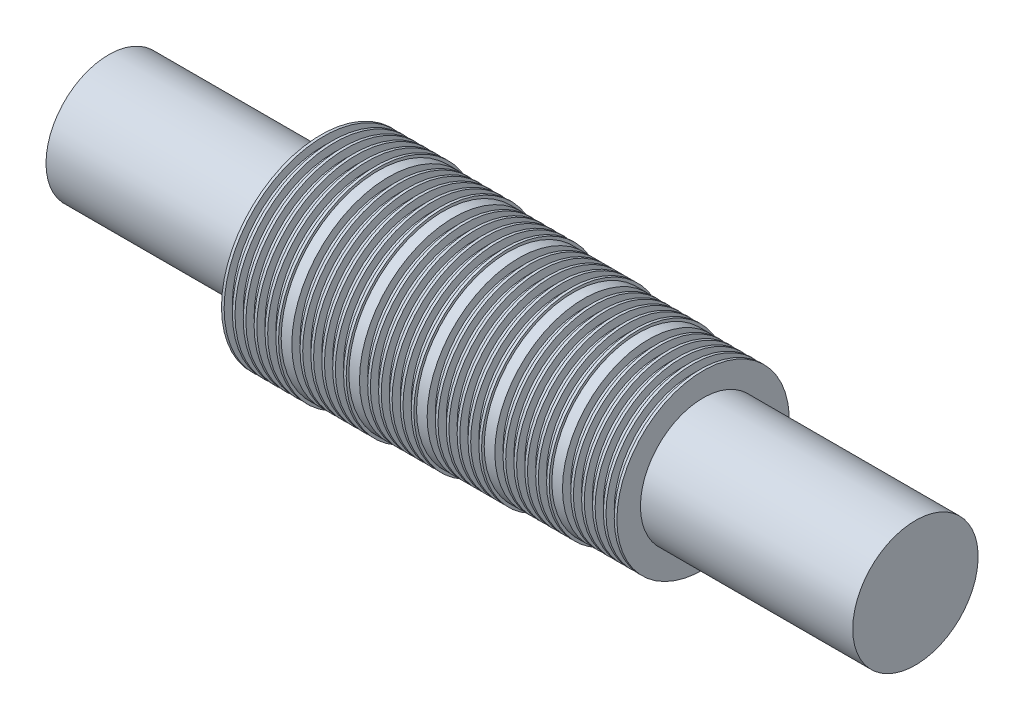
SolidWorks part; units mm, degrees
ref_plane "Front Plane" through (0, 0, 0) normal (0, 0, 1) x (1, 0, 0)
ref_plane "Top Plane" through (0, 0, 0) normal (0, 1, 0) x (1, 0, 0)
ref_plane "Right Plane" through (0, 0, 0) normal (1, 0, 0) x (0, 0, -1)
sketch "Sketch1" plane through (0, 0, 0) normal (0, 0, 1) x (1, 0, 0)
  line L24 (20.574, 9.525) -> (20.574, 8.7376)
  line L25 (20.574, 8.7376) -> (21.3614, 8.7376)
  line L26 (21.3614, 8.7376) -> (21.3614, 9.525)
  line L27 (21.3614, 9.525) -> (21.6154, 9.525)
  line L28 (21.6154, 9.525) -> (21.6154, 8.7376)
  line L29 (21.6154, 8.7376) -> (22.4028, 8.7376)
  line L30 (22.4028, 8.7376) -> (22.4028, 9.525)
  line L31 (22.4028, 9.525) -> (22.6568, 9.525)
  line L32 (22.6568, 9.525) -> (22.6568, 8.7376)
  line L33 (22.6568, 8.7376) -> (23.4442, 8.7376)
  line L34 (23.4442, 8.7376) -> (23.4442, 9.525)
  line L35 (23.4442, 9.525) -> (23.6982, 9.525)
  line L36 (23.6982, 9.525) -> (23.6982, 8.7376)
  line L37 (23.6982, 8.7376) -> (24.4856, 8.7376)
  line L38 (24.4856, 8.7376) -> (24.4856, 9.525)
  line L39 (24.4856, 9.525) -> (24.7396, 9.525)
  line L40 (24.7396, 9.525) -> (24.7396, 8.7376)
  line L41 (24.7396, 8.7376) -> (25.527, 8.7376)
  line L42 (25.527, 8.7376) -> (25.527, 9.525)
  line L43 (25.527, 9.525) -> (25.781, 9.525)
  line L44 (25.781, 9.525) -> (25.781, 9.271)
  line L45 (25.781, 9.271) -> (26.797, 9.271)
  line L46 (26.797, 9.271) -> (26.797, 8.4836)
  line L47 (26.797, 8.4836) -> (27.5844, 8.4836)
  line L48 (27.5844, 8.4836) -> (27.5844, 9.271)
  line L49 (27.5844, 9.271) -> (27.8384, 9.271)
  line L50 (27.8384, 9.271) -> (27.8384, 8.4836)
  line L51 (27.8384, 8.4836) -> (28.6258, 8.4836)
  line L52 (28.6258, 8.4836) -> (28.6258, 9.271)
  line L53 (28.6258, 9.271) -> (28.8798, 9.271)
  line L54 (28.8798, 9.271) -> (28.8798, 8.4836)
  line L55 (28.8798, 8.4836) -> (29.6672, 8.4836)
  line L56 (29.6672, 8.4836) -> (29.6672, 9.271)
  line L57 (29.6672, 9.271) -> (29.9212, 9.271)
  line L58 (29.9212, 9.271) -> (29.9212, 8.4836)
  line L59 (29.9212, 8.4836) -> (30.7086, 8.4836)
  line L60 (30.7086, 8.4836) -> (30.7086, 9.271)
  line L61 (30.7086, 9.271) -> (30.9626, 9.271)
  line L62 (30.9626, 9.271) -> (30.9626, 8.4836)
  line L63 (30.9626, 8.4836) -> (31.75, 8.4836)
  line L64 (31.75, 8.4836) -> (31.75, 9.271)
  line L65 (31.75, 9.271) -> (32.004, 9.271)
  line L66 (32.004, 9.271) -> (32.004, 9.017)
  line L67 (32.004, 9.017) -> (33.02, 9.017)
  line L68 (33.02, 9.017) -> (33.02, 8.2296)
  line L69 (33.02, 8.2296) -> (33.8074, 8.2296)
  line L70 (33.8074, 8.2296) -> (33.8074, 9.017)
  line L71 (33.8074, 9.017) -> (34.0614, 9.017)
  line L72 (34.0614, 9.017) -> (34.0614, 8.2296)
  line L73 (34.0614, 8.2296) -> (34.8488, 8.2296)
  line L74 (34.8488, 8.2296) -> (34.8488, 9.017)
  line L75 (34.8488, 9.017) -> (35.1028, 9.017)
  line L76 (35.1028, 9.017) -> (35.1028, 8.2296)
  line L77 (35.1028, 8.2296) -> (35.8902, 8.2296)
  line L78 (35.8902, 8.2296) -> (35.8902, 9.017)
  line L79 (35.8902, 9.017) -> (36.1442, 9.017)
  line L80 (36.1442, 9.017) -> (36.1442, 8.2296)
  line L81 (36.1442, 8.2296) -> (36.9316, 8.2296)
  line L82 (36.9316, 8.2296) -> (36.9316, 9.017)
  line L83 (36.9316, 9.017) -> (37.1856, 9.017)
  line L84 (37.1856, 9.017) -> (37.1856, 8.2296)
  line L85 (37.1856, 8.2296) -> (37.973, 8.2296)
  line L86 (37.973, 8.2296) -> (37.973, 9.017)
  line L87 (37.973, 9.017) -> (38.227, 9.017)
  line L88 (38.227, 9.017) -> (38.227, 8.763)
  line L89 (38.227, 8.763) -> (39.243, 8.763)
  line L90 (39.243, 8.763) -> (39.243, 7.9756)
  line L91 (39.243, 7.9756) -> (40.0304, 7.9756)
  line L92 (40.0304, 7.9756) -> (40.0304, 8.763)
  line L93 (40.0304, 8.763) -> (40.2844, 8.763)
  line L94 (40.2844, 8.763) -> (40.2844, 7.9756)
  line L95 (40.2844, 7.9756) -> (41.0718, 7.9756)
  line L96 (41.0718, 7.9756) -> (41.0718, 8.763)
  line L97 (41.0718, 8.763) -> (41.3258, 8.763)
  line L98 (41.3258, 8.763) -> (41.3258, 7.9756)
  line L99 (41.3258, 7.9756) -> (42.1132, 7.9756)
  line L100 (42.1132, 7.9756) -> (42.1132, 8.763)
  line L101 (42.1132, 8.763) -> (42.3672, 8.763)
  line L102 (42.3672, 8.763) -> (42.3672, 7.9756)
  line L103 (42.3672, 7.9756) -> (43.1546, 7.9756)
  line L104 (43.1546, 7.9756) -> (43.1546, 8.763)
  line L105 (43.1546, 8.763) -> (43.4086, 8.763)
  line L106 (43.4086, 8.763) -> (43.4086, 7.9756)
  line L107 (43.4086, 7.9756) -> (44.196, 7.9756)
  line L108 (44.196, 7.9756) -> (44.196, 8.763)
  line L109 (44.196, 8.763) -> (44.45, 8.763)
  line L110 (44.45, 8.763) -> (44.45, 8.509)
  line L111 (44.45, 8.509) -> (45.466, 8.509)
  line L112 (45.466, 8.509) -> (45.466, 7.7216)
  line L113 (45.466, 7.7216) -> (46.2534, 7.7216)
  line L114 (46.2534, 7.7216) -> (46.2534, 8.509)
  line L115 (46.2534, 8.509) -> (46.5074, 8.509)
  line L116 (46.5074, 8.509) -> (46.5074, 7.7216)
  line L117 (46.5074, 7.7216) -> (47.2948, 7.7216)
  line L118 (47.2948, 7.7216) -> (47.2948, 8.509)
  line L119 (47.2948, 8.509) -> (47.5488, 8.509)
  line L120 (47.5488, 8.509) -> (47.5488, 7.7216)
  line L121 (47.5488, 7.7216) -> (48.3362, 7.7216)
  line L122 (48.3362, 7.7216) -> (48.3362, 8.509)
  line L123 (48.3362, 8.509) -> (48.5902, 8.509)
  line L124 (48.5902, 8.509) -> (48.5902, 7.7216)
  line L125 (48.5902, 7.7216) -> (49.3776, 7.7216)
  line L126 (49.3776, 7.7216) -> (49.3776, 8.509)
  line L127 (49.3776, 8.509) -> (49.6316, 8.509)
  line L128 (49.6316, 8.509) -> (49.6316, 7.7216)
  line L129 (49.6316, 7.7216) -> (50.419, 7.7216)
  line L130 (50.419, 7.7216) -> (50.419, 8.509)
  line L131 (50.419, 8.509) -> (50.673, 8.509)
  line L132 (50.673, 8.509) -> (50.673, 8.255)
  line L133 (50.673, 8.255) -> (51.689, 8.255)
  line L134 (51.689, 8.255) -> (51.689, 7.4676)
  line L135 (51.689, 7.4676) -> (52.4764, 7.4676)
  line L136 (52.4764, 7.4676) -> (52.4764, 8.255)
  line L137 (52.4764, 8.255) -> (52.7304, 8.255)
  line L138 (52.7304, 8.255) -> (52.7304, 7.4676)
  line L139 (52.7304, 7.4676) -> (53.5178, 7.4676)
  line L140 (53.5178, 7.4676) -> (53.5178, 8.255)
  line L141 (53.5178, 8.255) -> (53.7718, 8.255)
  line L142 (53.7718, 8.255) -> (53.7718, 7.4676)
  line L143 (53.7718, 7.4676) -> (54.5592, 7.4676)
  line L144 (54.5592, 7.4676) -> (54.5592, 8.255)
  line L145 (54.5592, 8.255) -> (54.8132, 8.255)
  line L146 (54.8132, 8.255) -> (54.8132, 7.4676)
  line L147 (54.8132, 7.4676) -> (55.6006, 7.4676)
  line L148 (55.6006, 7.4676) -> (55.6006, 8.255)
  line L149 (55.6006, 8.255) -> (55.8546, 8.255)
  line L150 (55.8546, 8.255) -> (55.8546, 7.4676)
  line L151 (55.8546, 7.4676) -> (56.642, 7.4676)
  line L152 (56.642, 7.4676) -> (56.642, 8.255)
  line L153 (56.642, 8.255) -> (56.896, 8.255)
  line L156 (20.32, 6) -> (0, 6)
  line L157 (0, 6) -> (0, 0)
  line L158 (0, 0) -> (61.976, 0)
  line L160 (20.574, 9.525) -> (20.32, 9.525)
  line L161 (20.32, 9.525) -> (20.32, 6)
  line L162 (56.896, 6) -> (77.216, 6)
  line L163 (77.216, 6) -> (77.216, 0)
  line L164 (77.216, 0) -> (61.976, 0)
  line L165 (56.896, 8.255) -> (56.896, 6)
  point P5 (20.447, 9.525)
  point P6 (67.056, 6)
  dimension "D1" = 6
  dimension "D9" = 20.32
  dimension "D3" = 0.254
  dimension "D4" = 0.7874
  dimension "D5" = 0.7874
  dimension "D7" = 1.016
  dimension "D10" = 6
  dimension "D11" = 20.32
  dimension "D2" = 9.525
  dimension "D6" = 0.254
revolve "Revolve1" add sketch "Sketch1" angle 360 about L158
equation "\"kero_radius\"=0.23622in"
equation "\"D1@Sketch1\"=\"kero_radius\""
equation "\"lox_radius\"=0.23622in"
equation "\"Cavity_width\"=0.031in"
equation "\"tooth_width\"=0.01in"
equation "\"cavity_depth\"=0.031in"
equation "\"seal_step\"=0.01in"
equation "\"purge_length\"=0.04in"
equation "\"D3@Sketch1\"=\"tooth_width\""
equation "\"D4@Sketch1\"=\"Cavity_width\""
equation "\"D5@Sketch1\"=\"cavity_depth\""
equation "\"D7@Sketch1\"=\"purge_length\""
equation "\"D10@Sketch1\"=\"lox_radius\""
equation "\"lox_in_radius\"=.375in"
equation "\"bearing_radius\"= 0.629921"
equation "\"bearing_width\"=0.393701"
equation "\"insert_radius\" = 0.6in"
equation "\"recycle_groove width\" = 0.06in"
equation "\"recycle_groove_depth\" = 0.06in"
equation "\"N2_purge_width\"= .06in"
equation "\"N2_purge_depth\"= .06in"
equation "\"drain_width\"= .06in"
equation "\"drain_depth\"= .06in"
equation "\"radial_clearance\"= .002in"
equation "\"IPS_flange_width\"= .2in"
equation "\"IPS_flange_radius\" = 2.2in"
equation "\"IPS_LOX_male_radius\"= .9in"
equation "\"IPS_Kero_male_radius\" = .9in"
equation "\"IPS_radius\"= 1.4in"
equation "\"InsertLength\"= 1.445in"
equation "\"D2@Sketch1\"=\"lox_in_radius\""
equation "\"D6@Sketch1\"=\"seal_step\""
